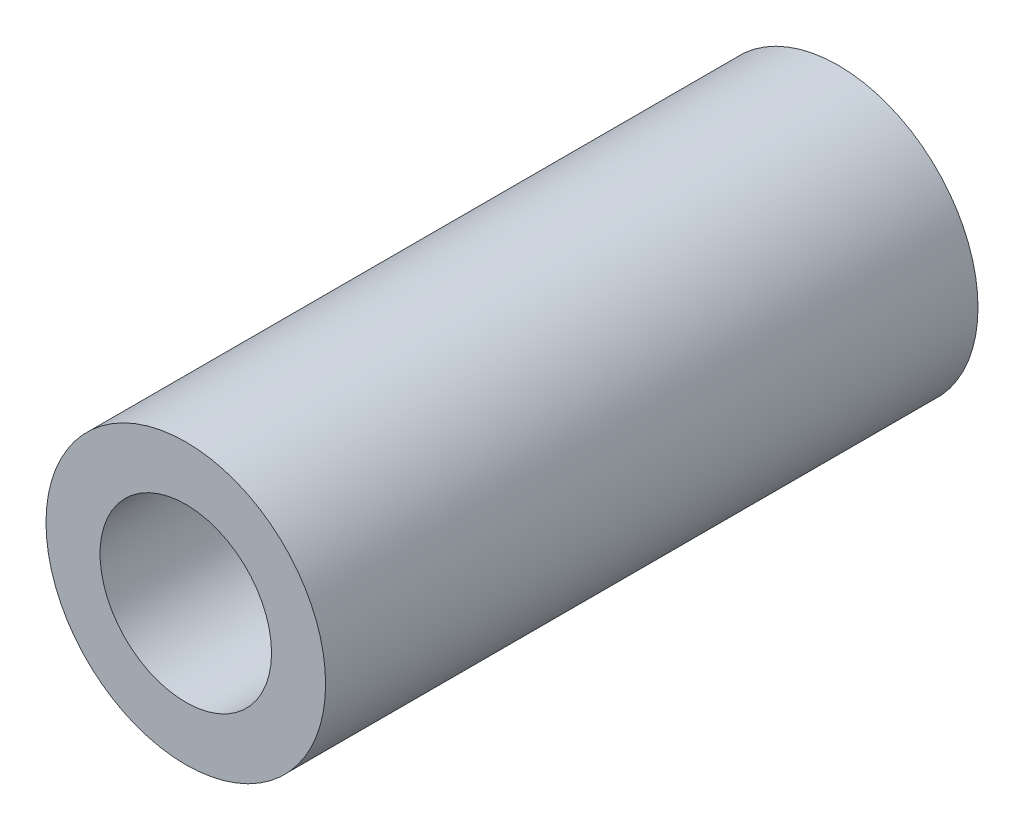
SolidWorks part; units mm, degrees
ref_plane "Front Plane" through (0, 0, 0) normal (0, 0, 1) x (1, 0, 0)
ref_plane "Top Plane" through (0, 0, 0) normal (0, 1, 0) x (1, 0, 0)
ref_plane "Right Plane" through (0, 0, 0) normal (1, 0, 0) x (0, 0, -1)
sketch "Sketch1" plane through (0, 0, 0) normal (0, 0, 1) x (1, 0, 0)
  circle A0 centre (0, 0) radius 2.3813
  circle A1 centre (0, 0) radius 1.4605
  dimension "OD" = 4.7625
  dimension "ID" = 2.921
extrude "Extrude1" add sketch "Sketch1" along normal mid plane 11.1125
sketch "Sketch2" plane through (0, 0, 0) normal (1, 0, 0) x (0, 0, -1)
  line L0 (-5.5562, -1.4605) -> (5.5562, -1.4605) construction
  line L3 (5.5562, 1.4605) -> (-5.5562, 1.4605) construction
  line L5 (-5.5562, -1.4605) -> (5.5562, -1.4605)
  line L6 (5.5562, 1.4605) -> (-5.5562, 1.4605)
sketch "Sketch4" plane through (0, 0, 5.5562) normal (0, 0, 1) x (1, 0, 0)
  line L0 (0, 0) -> (-1.0327, 1.0327)
  line L1 (0, -2.6194) -> (0, 2.6194) construction
  circle A0 centre (0, 0) radius 1.4605 construction
  dimension "D1" = 45
